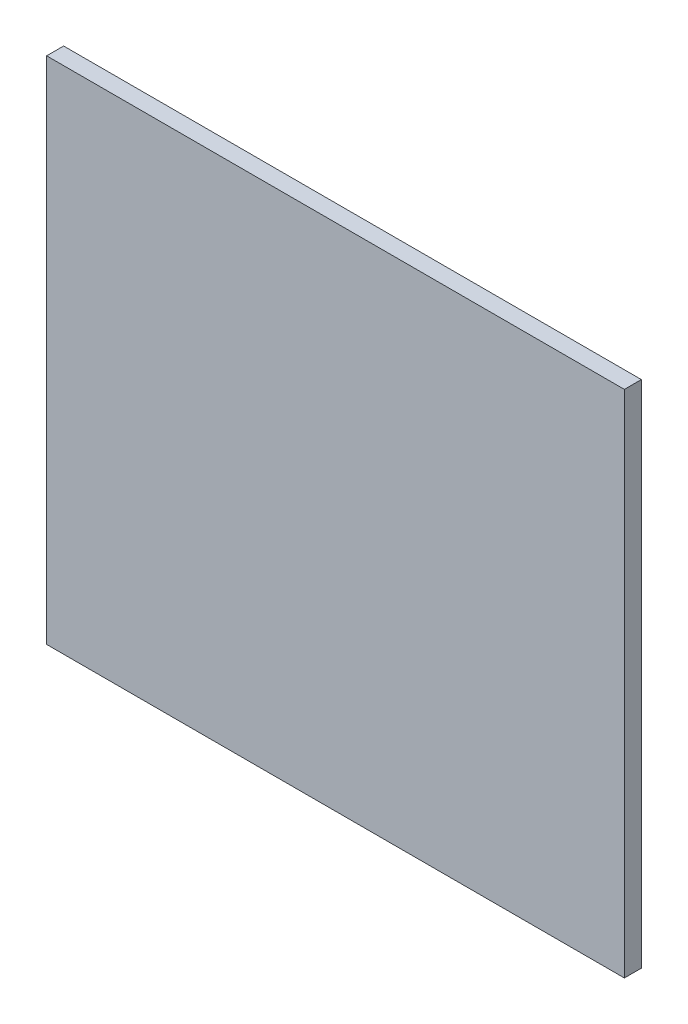
SolidWorks part; units mm, degrees
ref_plane "Front Plane" through (0, 0, 0) normal (0, 0, 1) x (1, 0, 0)
ref_plane "Top Plane" through (0, 0, 0) normal (0, 1, 0) x (1, 0, 0)
ref_plane "Right Plane" through (0, 0, 0) normal (1, 0, 0) x (0, 0, -1)
sketch "Sketch1" plane through (0, 0, 0) normal (0, 0, 1) x (1, 0, 0)
  line L1 (-170, -150) -> (170, -150)
  line L2 (-170, -150) -> (-170, 150)
  line L3 (-170, 150) -> (170, 150)
  line L4 (170, -150) -> (170, 150)
  line L5 (-170, -150) -> (170, 150) construction
  line L6 (-170, 150) -> (170, -150) construction
  point P0 (0, 0)
  dimension "D1" = 340
  dimension "D2" = 300
extrude "Boss-Extrude1" add sketch "Sketch1" along normal blind 10
equation "\"PCWidth\"= 172mm"
equation "\"PCLength\"= 320mm"
equation "\"PCHeight\"= 242mm"
equation "\"WallThickness\"= 10mm"
equation "\"ThermoBarrierThickness\"= 3mm"
equation "\"HotSideGap\"= 50mm"
equation "\"PCClearance\"= 25mm"
equation "\"D1@Sketch1\"=\"PCLength\" + (2 * \"WallThickness\")"
equation "\"D2@Sketch1\"=\"RadiatorHeight\" + \"PCClearance\""
equation "\"D1@Boss-Extrude1\"=\"WallThickness\""
equation "\"RadiatorHeight\"= 275mm"
